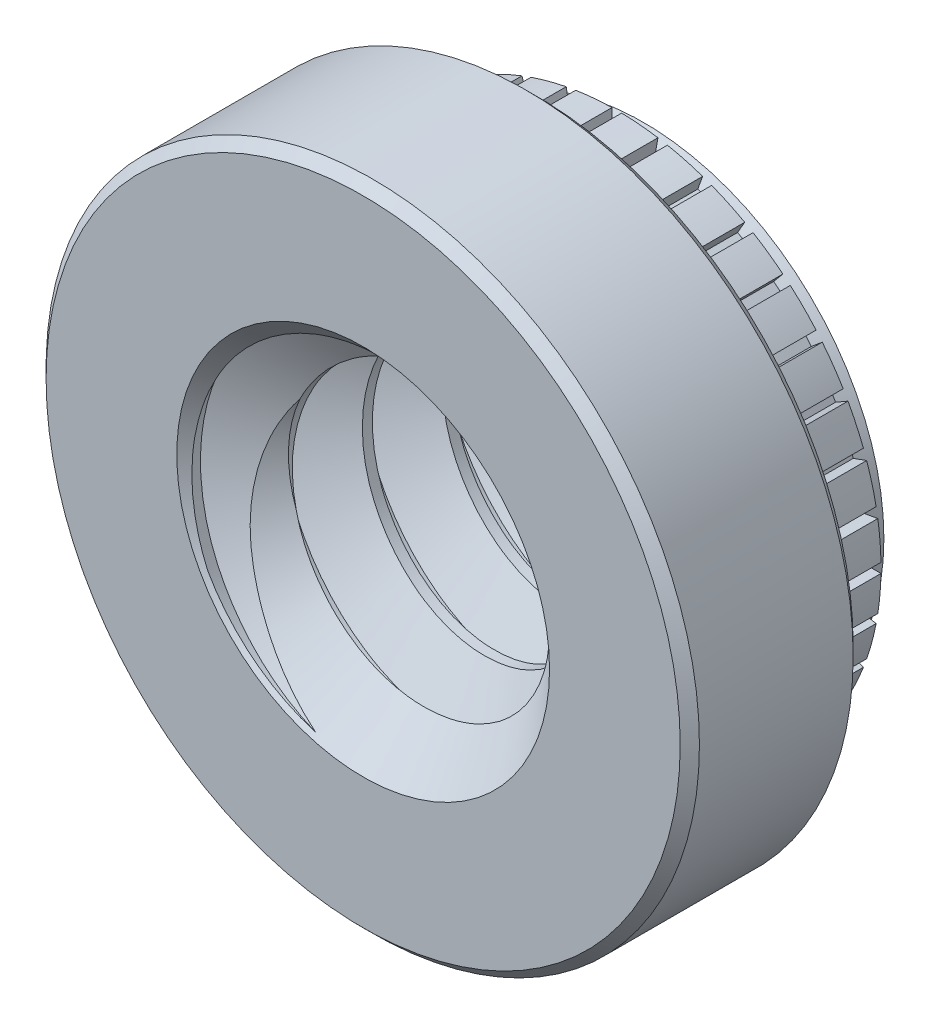
SolidWorks part; units mm, degrees
ref_plane "Front Plane" through (0, 0, 0) normal (0, 0, 1) x (1, 0, 0)
ref_plane "Top Plane" through (0, 0, 0) normal (0, 1, 0) x (1, 0, 0)
ref_plane "Right Plane" through (0, 0, 0) normal (1, 0, 0) x (0, 0, -1)
sketch "Sketch1" plane through (0, 0, 0) normal (0, 0, 1) x (1, 0, 0)
  circle A0 centre (0, 0) radius 4.318
  dimension "A" = 8.636
extrude "Extrude1" add sketch "Sketch1" against normal blind 2.286
sketch "Sketch15" plane through (0, 0, -2.286) normal (0, 0, -1) x (-1, 0, 0)
  circle A0 centre (0, 0) radius 3.175
  dimension "hole dia" = 6.35
sketch "Sketch2" plane through (0, 0, -2.286) normal (0, 0, -1) x (-1, 0, 0)
  circle A0 centre (0, 0) radius 3.4925
  dimension "D1" = 6.985
extrude "Extrude2" add sketch "Sketch2" along normal blind 1.4224
sketch "Sketch3" plane through (0, 0, -3.7084) normal (0, 0, -1) x (-1, 0, 0)
  line L0 (0, 3.302) -> (0, 4.318)
  circle A1 centre (0, 0) radius 4.318 construction
  circle A2 centre (0, 0) radius 3.302
  circle A3 centre (0, 0) radius 3.302 construction
  dimension "D1" = 0.1905
extrude "Cut-Extrude-Thin1" cut sketch "Sketch3" against normal up to surface (1.4224 mm away) thin up to face at (4.318, 0, -2.286) thin type mid plane wall 0.127
pattern_circular "CirPattern1" count 36 over 360 about axis through (0, 0, 0) along (0, 0, 1) of "Cut-Extrude-Thin1"
sketch "Sketch5" plane through (0, 0, -3.7084) normal (0, 0, -1) x (-1, 0, 0)
  circle A0 centre (0, 0) radius 4.318 construction
  circle A3 centre (0, 0) radius 3.175
  dimension "C" = 6.35
extrude "Cut-Extrude1" cut sketch "Sketch5" against normal blind 0.3556 draft 20 flip side to cut draft outward yes
chamfer "Chamfer2" distance 0.127 angle 45 2 edges at (4.318, 0, 0) (4.318, 0, -2.286)
sketch "Sketch7" plane through (0, 0, 0) normal (0, 0, 1) x (1, 0, 0)
  circle A0 centre (0, 0) radius 2.413
  dimension "Thread Od" = 4.826
extrude "Cut-Extrude3" cut sketch "Sketch7" against normal through all
sketch "Sketch8" plane through (0, 0, -3.7084) normal (0, 0, -1) x (-1, 0, 0)
  circle A0 centre (0, 0) radius 2.413 construction
  circle A1 centre (0, 0) radius 2.413
curve "Helix/Spiral1" pitch 1.0583 height 6.8834 turns 6.504 parameters "pitch"=1.0583
sketch "Sketch9" plane through (0, 0, 0) normal (1, 0, 0) x (0, 0, -1)
  line L0 (4.6344, 2.413) -> (4.2376, 1.7256)
  line L1 (4.2376, 1.7256) -> (4.1053, 1.7256)
  line L2 (4.1053, 1.7256) -> (3.7084, 2.413)
  line L3 (4.6344, 2.413) -> (3.7084, 2.413)
  line L4 (4.1714, 2.413) -> (4.1714, 1.7256) construction
  line L5 (4.436, 2.0693) -> (3.9068, 2.0693) construction
  line L6 (3.7084, -2.413) -> (3.7084, 2.413) construction
  dimension "D1" = 60
  dimension "D2" = 0.1323
  dimension "D3" = 0.5292
sweep "Sweep1" add profiles "Sketch9" path "Helix/Spiral1"
sketch "Sketch10" plane through (0, 0, 0) normal (0, 0, 1) x (1, 0, 0)
  circle A0 centre (0, 0) radius 4.318 construction
  circle A1 centre (0, 0) radius 4.318
extrude "Cut-Extrude4" cut sketch "Sketch10" along normal through all
sketch "Sketch11" plane through (0, 0, -3.7084) normal (0, 0, -1) x (-1, 0, 0)
  circle A1 centre (0, 0) radius 3.175 construction
  circle A2 centre (0, 0) radius 3.175
extrude "Cut-Extrude5" cut sketch "Sketch11" along normal through all
sketch "Sketch13" plane through (0, 0, 0) normal (0, 0, 1) x (1, 0, 0)
  circle A2 centre (0, 0) radius 2.4638
  circle A3 centre (0, 0) radius 2.4638
  dimension "D1" = 0.0508
extrude "Cut-Extrude6" cut sketch "Sketch13" against normal through all draft 45
sketch "Sketch14" plane through (0, 0, -3.7084) normal (0, 0, -1) x (-1, 0, 0)
  circle A2 centre (0, 0) radius 2.4638
  circle A3 centre (0, 0) radius 2.4638
  dimension "D1" = 0.0508
extrude "Cut-Extrude7" cut sketch "Sketch14" against normal through all draft 45
equation "\"D3@Helix/Spiral1\" = \"B@Extrude1\"+\"panel min.@Extrude2\"+.125"
equation "\"D2@Sketch9\" = \"pitch@Helix/Spiral1\"*.125"
equation "\"D3@Sketch9\" = \"pitch@Helix/Spiral1\"*.50"
equation "\"D1@Sketch2\" = \"hole dia@Sketch15\"+.025"
equation "\"D1@Cut-Extrude1\" = \"panel min.@Extrude2\"*.25"
